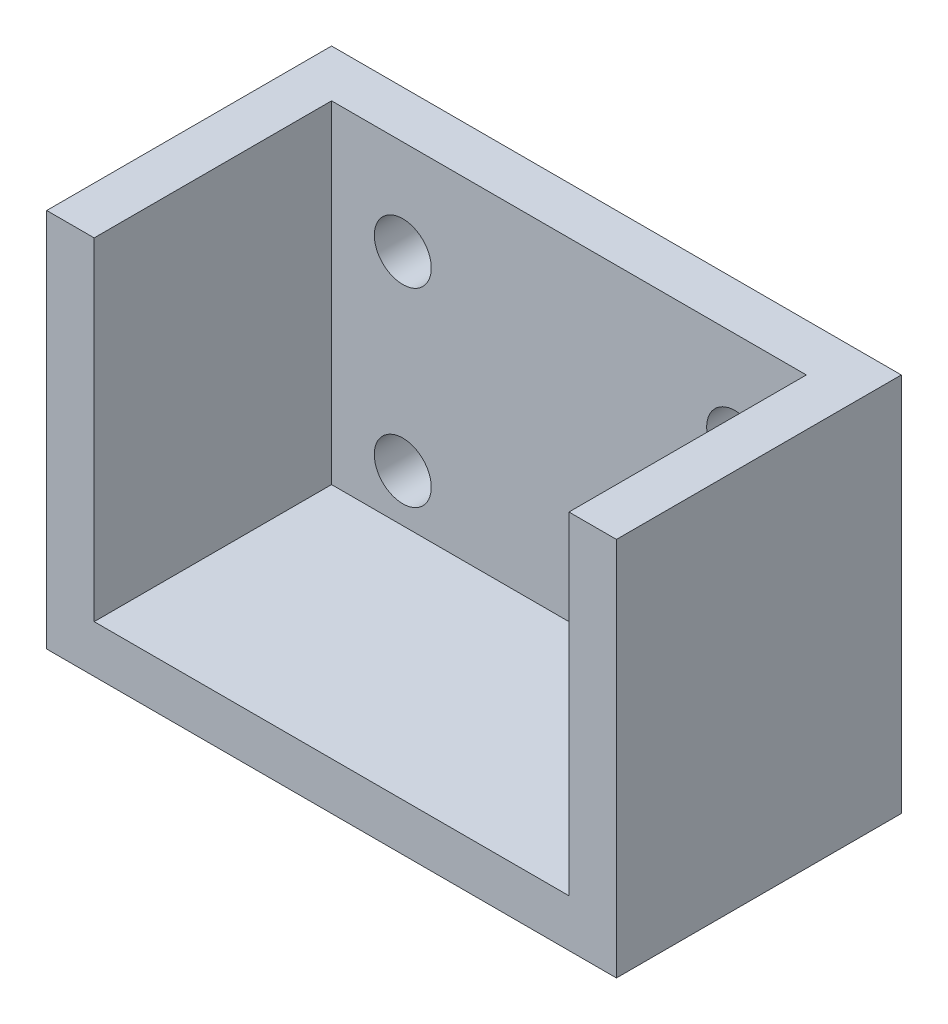
SolidWorks part; units mm, degrees
ref_plane "Спереди" through (0, 0, 0) normal (0, 0, 1) x (1, 0, 0)
ref_plane "Сверху" through (0, 0, 0) normal (0, 1, 0) x (1, 0, 0)
ref_plane "Справа" through (0, 0, 0) normal (1, 0, 0) x (0, 0, -1)
sketch "Эскиз1" plane through (0, 0, 0) normal (0, 1, 0) x (1, 0, 0)
  line L1 (0, 0) -> (60, 0)
  line L2 (0, 0) -> (0, 30)
  line L3 (0, 30) -> (60, 30)
  line L4 (60, 0) -> (60, 30)
  dimension "D1" = 30
  dimension "D2" = 60
extrude "Бобышка-Вытянуть1" add sketch "Эскиз1" along normal blind 5
sketch "Эскиз3" plane through (0, 5, 0) normal (0, 1, 0) x (1, 0, 0)
  line L0 (5, 25) -> (55, 25)
  line L1 (55, 25) -> (55, 0)
  line L2 (0, 0) -> (60, 0) construction
  line L3 (55, 0) -> (60, 0)
  line L4 (60, 0) -> (60, 30)
  line L5 (60, 30) -> (0, 30)
  line L6 (0, 30) -> (0, 0)
  line L7 (0, 0) -> (5, 0)
  line L8 (5, 0) -> (5, 25)
  dimension "D1" = 5
  dimension "D2" = 5
  dimension "D3" = 5
  dimension "D4" = 25
extrude "Бобышка-Вытянуть2" add sketch "Эскиз3" along normal blind 35
sketch "Эскиз4" plane through (0, 0, -30) normal (0, 0, -1) x (-1, 0, 0)
  line L0 (-30, 0) -> (-30, 40) construction
  line L1 (-60, 0) -> (0, 0) construction
  line L2 (-60, 40) -> (0, 40) construction
  line L3 (0, 10) -> (-60, 10) construction
  line L4 (0, 40) -> (0, 0) construction
  line L5 (-60, 40) -> (-60, 0) construction
  line L6 (-60, 30) -> (0, 30) construction
  circle A0 centre (-12.5, 10) radius 3
  circle A1 centre (-12.5, 30) radius 3
  circle A2 centre (-47.5, 30) radius 3
  circle A3 centre (-47.5, 10) radius 3
  dimension "D3" = 6
  dimension "D1" = 10
  dimension "D2" = 10
  dimension "D4" = 35
  dimension "D5" = 35
extrude "Вырез-Вытянуть1" cut sketch "Эскиз4" against normal up to surface (5 mm away) up to face at (30, 22.5, -25)
